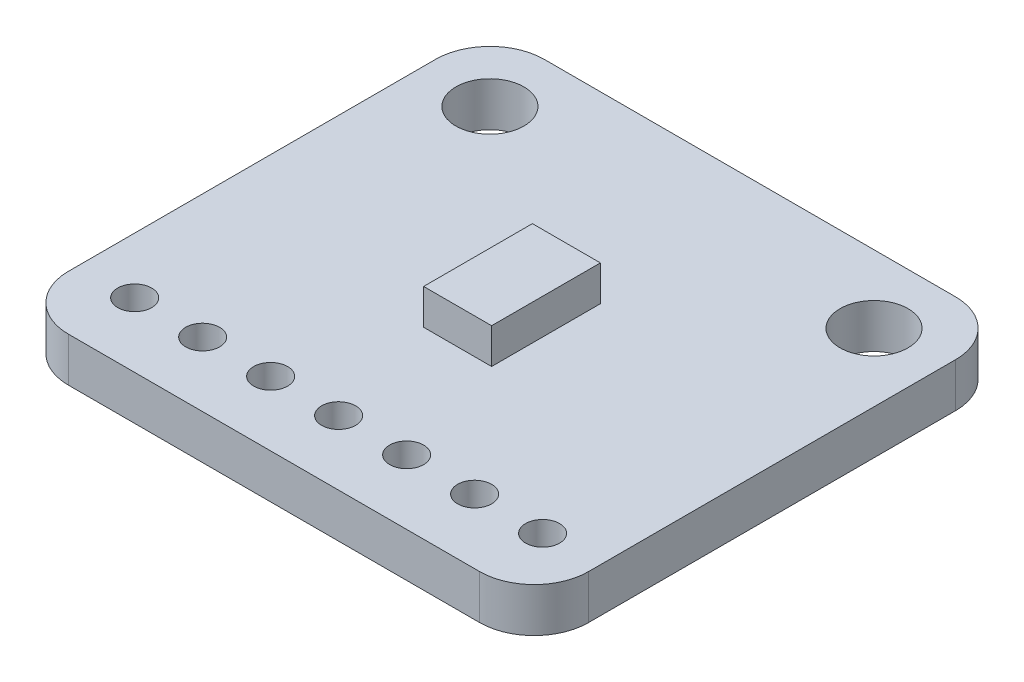
SolidWorks part; units mm, degrees
ref_plane "Front Plane" through (0, 0, 0) normal (0, 0, 1) x (1, 0, 0)
ref_plane "Top Plane" through (0, 0, 0) normal (0, 1, 0) x (1, 0, 0)
ref_plane "Right Plane" through (0, 0, 0) normal (1, 0, 0) x (0, 0, -1)
sketch "Sketch1" plane through (0, 0, 0) normal (0, 1, 0) x (1, 0, 0)
  line L0 (0, 2.413) -> (19.431, 2.413) construction
  line L1 (2.032, 0) -> (17.399, 0)
  line L2 (0, 2.032) -> (0, 15.748)
  line L3 (2.032, 17.78) -> (17.399, 17.78)
  line L4 (19.431, 2.032) -> (19.431, 15.748)
  circle A0 centre (2.54, 15.24) radius 1.27
  circle A1 centre (16.891, 15.24) radius 1.27
  circle A2 centre (2.0955, 2.413) radius 0.635
  circle A3 centre (4.6355, 2.413) radius 0.635
  circle A4 centre (7.1755, 2.413) radius 0.635
  circle A5 centre (9.7155, 2.413) radius 0.635
  circle A6 centre (12.2555, 2.413) radius 0.635
  circle A7 centre (14.7955, 2.413) radius 0.635
  circle A8 centre (17.3355, 2.413) radius 0.635
  arc A9 (2.032, 0) -> (0, 2.032) centre (2.032, 2.032) cw
  arc A10 (17.399, 0) -> (19.431, 2.032) centre (17.399, 2.032) ccw
  arc A11 (19.431, 15.748) -> (17.399, 17.78) centre (17.399, 15.748) ccw
  arc A12 (0, 15.748) -> (2.032, 17.78) centre (2.032, 15.748) cw
  point P29 (0, 0)
  point P32 (19.431, 0)
  point P37 (0, 17.78)
  dimension "D3" = 1.27
  dimension "D4" = 1.27
  dimension "D5" = 1.27
  dimension "D6" = 1.27
  dimension "D7" = 1.27
  dimension "D8" = 1.27
  dimension "D9" = 1.27
  dimension "D10" = 2.54
  dimension "D11" = 2.54
  dimension "D15" = 2.54
  dimension "D16" = 2.54
  dimension "D17" = 2.413
  dimension "D18" = 2.54
  dimension "D19" = 2.54
  dimension "D20" = 2.54
  dimension "D21" = 2.54
  dimension "D22" = 2.54
  dimension "D23" = 2.032
  dimension "D1" = 17.78
  dimension "D2" = 19.431
  dimension "D12" = 2.54
  dimension "D13" = 2.54
  dimension "D14" = 2.54
extrude "Boss-Extrude1" add sketch "Sketch1" along normal blind 1.651
sketch "Sketch2" plane through (0, 1.651, 0) normal (0, 1, 0) x (1, 0, 0)
  line L0 (0.5952, 17.1848) -> (18.8358, 0.5952) construction
  line L2 (9.7155, 8.89) -> (8.4455, 8.89)
  line L3 (9.7155, 8.89) -> (9.7155, 6.858)
  line L4 (9.7155, 6.858) -> (8.4455, 6.858)
  line L5 (8.4455, 8.89) -> (8.4455, 6.858)
  line L6 (8.4455, 6.858) -> (10.9855, 6.858)
  line L7 (8.4455, 6.858) -> (8.4455, 10.922)
  line L8 (8.4455, 10.922) -> (10.9855, 10.922)
  line L9 (10.9855, 6.858) -> (10.9855, 10.922)
  arc A0 (2.032, 17.78) -> (0, 15.748) centre (2.032, 15.748) ccw construction
  arc A1 (17.399, 0) -> (19.431, 2.032) centre (17.399, 2.032) ccw construction
  dimension "D1" = 2.032
  dimension "D2" = 4.064
  dimension "D3" = 1.27
  dimension "D4" = 2.54
extrude "Boss-Extrude2" add sketch "Sketch2" along normal blind 1.3208 contours L2 L5 L4 L3 | L7 L0 L9 L8 | L0 L3 L6 L9 | L0 L7 L2 region at (9.9561, 1.651, -9.7966) region at (8.8688, 1.651, -9.275) region at (9.0805, 1.651, -7.874) region at (10.2665, 1.651, -7.6235)
